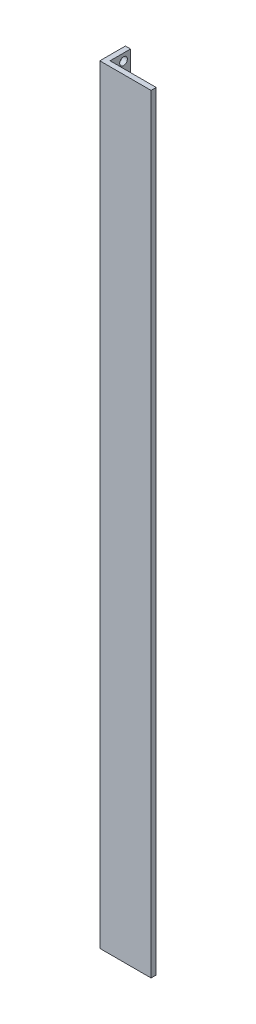
SolidWorks part; units mm, degrees
ref_plane "Front Plane" through (0, 0, 0) normal (0, 0, 1) x (1, 0, 0)
ref_plane "Top Plane" through (0, 0, 0) normal (0, 1, 0) x (1, 0, 0)
ref_plane "Right Plane" through (0, 0, 0) normal (1, 0, 0) x (0, 0, -1)
sketch "Sketch1" plane through (0, 0, 0) normal (0, 1, 0) x (1, 0, 0)
  line L0 (0, 0) -> (0, 10)
  line L1 (0, 10) -> (2, 10)
  line L2 (2, 10) -> (2, 2)
  line L3 (2, 2) -> (20, 2)
  line L4 (20, 2) -> (20, 0)
  line L5 (20, 0) -> (0, 0)
extrude "Boss-Extrude1" add sketch "Sketch1" along normal blind 300
sketch "Sketch2" plane through (0, 0, 0) normal (-1, 0, 0) x (0, 0, 1)
  circle A0 centre (-7.2626, 297.2454) radius 1.5
  circle A1 centre (-7.2585, 88.7434) radius 1.5
extrude "Cut-Extrude1" cut sketch "Sketch2" against normal through all
hole_wizard "Ø3.0 (3) Diameter Hole1" positions "Sketch3" profile "Sketch4" hole size "Ø3.0" standard "ISO" end condition through all
sketch "Sketch3" plane through (2, -25.4076, 52.862) normal (1, 0, 0) x (0, 0, -1)
  point P0 (58.862, 61.4076)
  point P1 (58.862, 37.4076)
sketch "Sketch4" plane through (2, 36, -6) normal (0, 1, 0) x (0, 0, -1)
  line L0 (0, 0) -> (0, 2)
  line L1 (0, 2) -> (1.5, 2)
  line L2 (1.5, 2) -> (1.5, 0)
  line L5 (1.5, 0) -> (0, 0)
  line L11 (0, -6.35) -> (0, 107.95) construction
  dimension "Thru Hole Dia." = 3
  dimension "Thru Hole Depth" = 2
